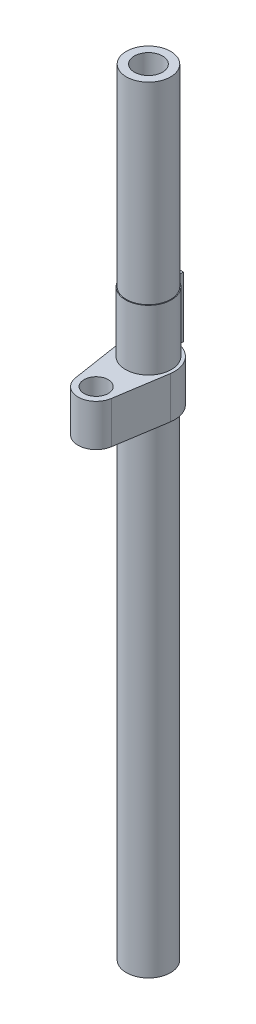
SolidWorks part; units mm, degrees
ref_plane "Ön Düzlem" through (0, 0, 0) normal (0, 0, 1) x (1, 0, 0)
ref_plane "Üst Düzlem" through (0, 0, 0) normal (0, 1, 0) x (1, 0, 0)
ref_plane "Sağ Düzlem" through (0, 0, 0) normal (1, 0, 0) x (0, 0, -1)
sketch "Sketch1" plane through (0, 0, 0) normal (0, 1, 0) x (1, 0, 0)
  circle A0 centre (0, 0) radius 2.75
  dimension "D1" = 5.5
extrude "Boss-Extrude1" add sketch "Sketch1" along normal blind 96.4
sketch "Sketch2" plane through (0, 0, 0) normal (0, -1, 0) x (1, 0, 0)
  circle A0 centre (0, 0) radius 1.75
  dimension "D1" = 3.5
extrude "Cut-Extrude1" cut sketch "Sketch2" against normal blind 8.9
extrude "Cut-Extrude2" cut sketch "Sketch2<2>" along normal blind 8.9 from surface starting at face at (0, 96.4, 2.75)
sketch "Sketch2<2>" plane through (0, 0, 0) normal (0, -1, 0) x (1, 0, 0) same geometry as "Sketch2"
ref_plane "Plane1" through (-2.75, 0, 0) normal (-1, 0, 0) x (0, 0, 1)
sketch "Sketch3" plane through (-2.75, 0, 0) normal (-1, 0, 0) x (0, 0, 1)
  line L0 (0, 6.15) -> (0, 0) construction
  line L1 (2.75, 96.4) -> (-2.75, 96.4) construction
  circle A0 centre (0, 6.15) radius 1.75
  circle A1 centre (0, 90.25) radius 1.75
  dimension "D2" = 3.5
  dimension "D1" = 6.15
  dimension "D3" = 6.15
extrude "Cut-Extrude3" cut sketch "Sketch3" against normal up to surface (2.75 mm away) up to face at (0, 87.5, 1.75)
ref_plane "Plane2" through (0, 72.45, 0) normal (0, 1, 0) x (1, 0, 0)
sketch "Sketch4" plane through (0, 72.45, 0) normal (0, 1, 0) x (1, 0, 0)
  line L0 (-0.75, 2.9047) -> (-0.75, 3.9047) construction
  line L1 (0.75, 2.9047) -> (0.75, 3.9047) construction
  line L2 (-0.75, 3.4047) -> (0.75, 3.4047) construction
  line L3 (-0.75, 3.9047) -> (0.75, 3.9047) construction
  line L4 (0.6, 2.7861) -> (0.6, 3.7547)
  line L5 (-0.6, 3.7547) -> (0.6, 3.7547)
  line L6 (-0.6, 2.7861) -> (-0.6, 3.7547)
  arc A0 (-0.75, 2.9047) -> (0.75, 2.9047) centre (0, 0) ccw construction
  arc A1 (-0.6, 2.7861) -> (0.6, 2.7861) centre (0, 0) ccw
  circle A2 centre (0, 0) radius 2.75 construction
  circle A3 centre (0, 0) radius 2.75
  point P9 (0, 3.4047)
  dimension "D1" = 6
  dimension "D2" = 1.5
  dimension "D3" = 1
  dimension "D4" = 0.15
extrude "Boss-Extrude2" add sketch "Sketch4" against normal blind 7.5
sketch "Sketch5" plane through (0, 64.95, 0) normal (0, -1, 0) x (1, 0, 0)
  line L0 (-3.2113, 0.5) -> (-2.2232, 6.8462)
  line L1 (2.2232, 6.8462) -> (3.2113, 0.5)
  arc A0 (2.2232, 6.8462) -> (-2.2232, 6.8462) centre (0, 6.5) ccw
  arc A1 (-3.2113, 0.5) -> (3.2113, 0.5) centre (0, 0) ccw
  circle A2 centre (0, 6.5) radius 1.5
  circle A3 centre (0, 0) radius 2.75 construction
  circle A4 centre (0, 0) radius 2.75
  dimension "D1" = 4.5
  dimension "D3" = 6.5
  dimension "D4" = 3
  dimension "D2" = 6.5
extrude "Boss-Extrude3" add sketch "Sketch5" along normal blind 5.2
